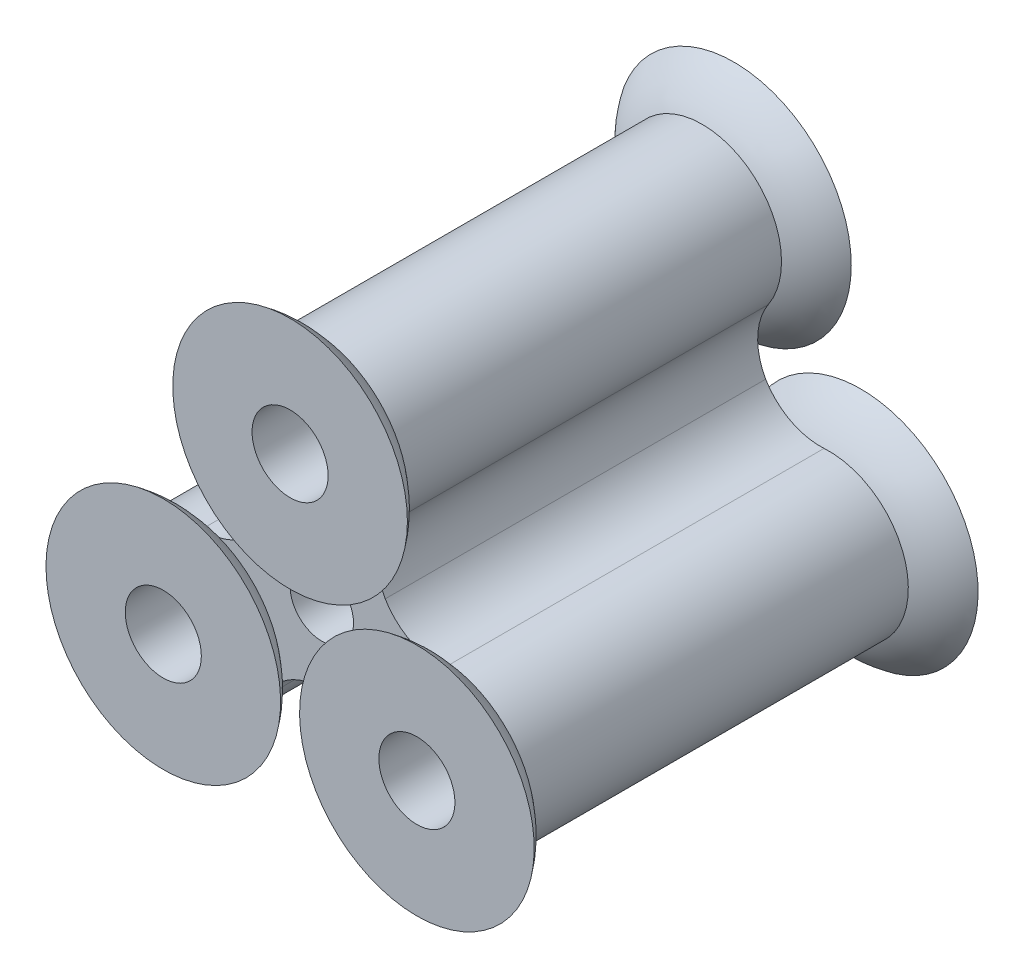
SolidWorks part; units mm, degrees
ref_plane "Front Plane" through (0, 0, 0) normal (0, 0, 1) x (1, 0, 0)
ref_plane "Top Plane" through (0, 0, 0) normal (0, 1, 0) x (1, 0, 0)
ref_plane "Right Plane" through (0, 0, 0) normal (1, 0, 0) x (0, 0, -1)
sketch "Sketch1" plane through (0, 0, 0) normal (0, 0, 1) x (1, 0, 0)
  line L1 (19.9965, -11.545) -> (0, 23.09)
  line L2 (0, 23.09) -> (-19.9965, -11.545)
  line L3 (-19.9965, -11.545) -> (19.9965, -11.545)
  circle A0 centre (0, 0) radius 11.545 construction
  circle A1 centre (0, 23.09) radius 12.5
  circle A2 centre (19.9965, -11.545) radius 12.5
  circle A3 centre (-19.9965, -11.545) radius 12.5
  circle A4 centre (0, 23.09) radius 6
  circle A5 centre (19.9965, -11.545) radius 6
  circle A6 centre (-19.9965, -11.545) radius 6
  circle A7 centre (0, 0) radius 5
  point P13 (0, 0)
  point P14 (0, 0)
  point P15 (0, 0)
  point P19 (0, 0)
  dimension "D1" = 23.09
  dimension "D2" = 25
  dimension "D4" = 12
  dimension "D6" = 10
  dimension "D3" = 3
  dimension "D5" = 3
extrude "Boss-Extrude1" add sketch "Sketch1" along normal blind 60 contours A6 L2 A3 L3 | A6 L3 A3 L2 | A3 L3 A2 L1 A1 L2 A7 | A4 L1 A1 L2 | A4 L2 A1 L1 | A5 L3 A2 L1 | A5 L1 A2 L3 region at (12.0321, -6.9467, 0) region at (15.6777, -3.3575, 0) region at (8.8562, -5.1132, 0) region at (0, 13.8934, 0) region at (4.9211, 15.2502, 0) region at (-30.5157, -17.6182, 0) region at (-12.0321, -6.9467, 0)
fillet "Fillet1" radius 10 2 edges at (13.7465, -0.7197, 30) (6.25, 12.2647, 30)
fillet "Fillet2" radius 9 4 edges at (-6.25, 12.2647, 30) (-13.7465, -0.7197, 30) (-7.4965, -11.545, 30) (7.4965, -11.545, 30)
sketch "Sketch2" plane through (0, 0, 0) normal (1, 0, 0) x (0, 0, -1)
  line L0 (-60, 35.59) -> (-60, 29.09)
  line L2 (-65, 29.09) -> (-60, 29.09)
  line L3 (-65, 29.09) -> (-65, 41.59)
  line L5 (-60, 23.09) -> (49000, 23.09) construction
  line L6 (-60, 35.59) -> (-60, 15.8751) construction
  arc A0 (-65, 41.59) -> (-60, 35.59) centre (-73.626, 29.3184) cw
  dimension "D4" = 15
  dimension "D2" = 5
  dimension "D3" = 12.5
revolve "Revolve3" add sketch "Sketch2" angle 360 about L5
pattern_circular "CirPattern1" count 3 over 360 about axis through (0, 0, 60) along (0, 0, -1) of "Revolve3"
ref_plane "Plane1" through (0, 0, 30) normal (0, 0, 1) x (1, 0, 0)
mirror "Mirror1" about plane through (0, 0, 30) normal (0, 0, 1) of "CirPattern1", "Revolve3"
